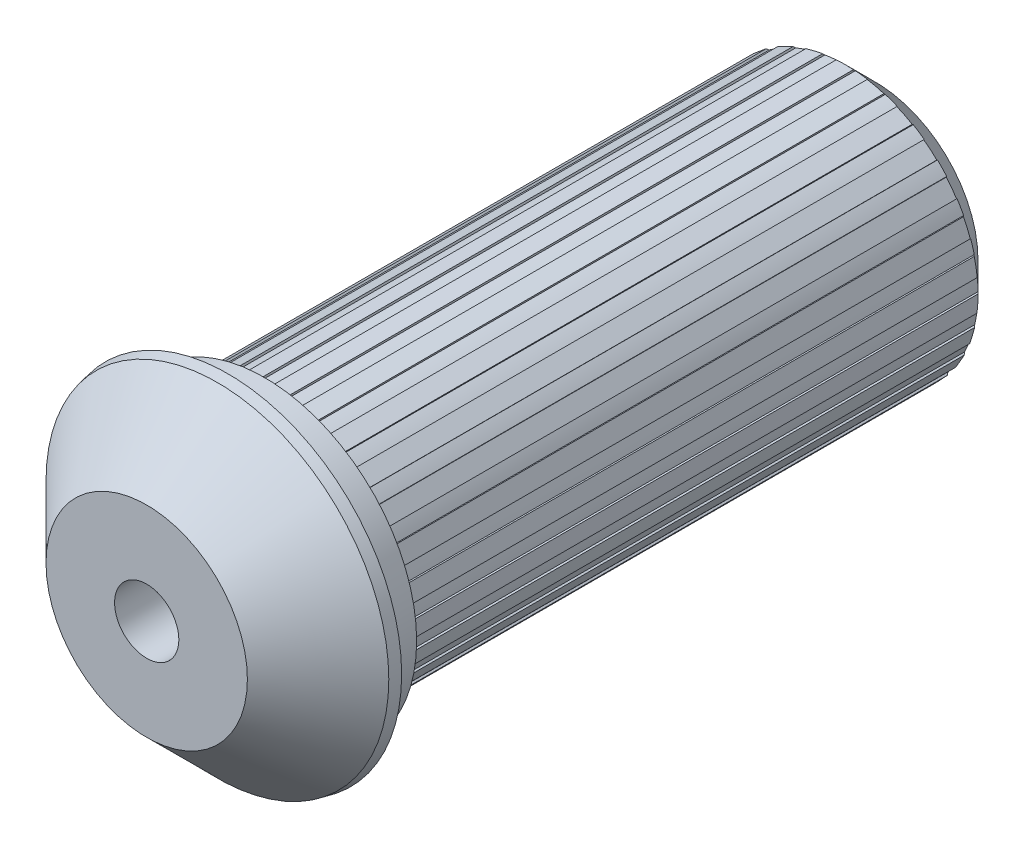
SolidWorks part; units mm, degrees
ref_plane "Front Plane" through (0, 0, 0) normal (0, 0, 1) x (1, 0, 0)
ref_plane "Top Plane" through (0, 0, 0) normal (0, 1, 0) x (1, 0, 0)
ref_plane "Right Plane" through (0, 0, 0) normal (1, 0, 0) x (0, 0, -1)
sketch "Sketch1" plane through (0, 0, 0) normal (0, 0, 1) x (1, 0, 0)
  line L0 (6.2, 2.4) -> (9.8, 2.4) construction
  line L1 (6.2, 2.4) -> (9.8, 2.4)
  arc A0 (6.2, 2.4) -> (9.8, 2.4) centre (8, 0) ccw construction
  arc A1 (6.2, 2.4) -> (9.8, 2.4) centre (8, 0) ccw
  circle A2 centre (8, 0) radius 6.075 construction
  circle A3 centre (8, 0) radius 6.075
extrude "Boss-Extrude1" add sketch "Sketch1" along normal up to surface (28.5 mm away)
sketch "Sketch2" plane through (0, 0, 28.5) normal (0, 0, 1) x (1, 0, 0)
  circle A0 centre (8, 0) radius 3
  circle A1 centre (8, 0) radius 1.5
  dimension "D1" = 3
extrude "Boss-Extrude2" add sketch "Sketch2" against normal up to surface (16.5 mm away)
sketch "Sketch3" plane through (0, 0, 28.5) normal (0, 0, 1) x (1, 0, 0)
  circle A0 centre (8, 0) radius 7.1 construction
  circle A1 centre (8, 0) radius 7.1
  circle A2 centre (8, 0) radius 1.5 construction
  circle A3 centre (8, 0) radius 1.5
extrude "Boss-Extrude3" add sketch "Sketch3" along normal offset from surface (5.5 mm away) 22 offset beyond the face yes
chamfer "Chamfer1" [suppressed] distance 1.2 angle 45
chamfer "Chamfer2" distance 2.4 angle 45 1 edges at (15.1, 0, 34)
sketch "Sketch4" plane through (0, 0, 0) normal (0, 0, -1) x (-1, 0, 0)
  circle A0 centre (-8, 0) radius 6.075 construction
  circle A1 centre (-8, 0) radius 6.075
  circle A2 centre (-8, 0) radius 6.125
  dimension "D1" = 12.25
extrude "Boss-Extrude4" add sketch "Sketch4" against normal up to surface (28.5 mm away) up to face at (15.1, 0, 28.5)
sketch "Sketch5" plane through (0, 0, 0) normal (0, 0, -1) x (-1, 0, 0)
  line L0 (-8, 0) -> (-8, 6.125) construction
  line L1 (-8, 0) -> (1.6155, 0) construction
  line L2 (-8.4, 6.05) -> (-7.6, 6.05)
  line L3 (-8.4, 6.05) -> (-8.4, 6.2)
  line L4 (-8.4, 6.2) -> (-7.6, 6.2)
  line L5 (-7.6, 6.05) -> (-7.6, 6.2)
  line L6 (-8.4, 6.05) -> (-7.6, 6.2) construction
  line L7 (-8.4, 6.2) -> (-7.6, 6.05) construction
  circle A0 centre (-8, 0) radius 6.125 construction
  dimension "D1" = 12.4
  dimension "D2" = 0.8
extrude "Boss-Extrude5" add sketch "Sketch5" against normal up to surface (28.5 mm away) up to face at (14.125, 0, 28.5)
pattern_circular "CirPattern1" count 27 over 360 about axis through (8, 0, 0) along (0, 0, 1) of "Boss-Extrude5"
sketch "Sketch6" plane through (0, 0, -27.3) normal (0, 1, 0) x (0, 0, 1)
  line L0 (61.3, 8) -> (24.9329, 8) construction
  line L1 (61.3, 3.3) -> (61.3, 12.7) construction
  line L2 (27.3, 12.8) -> (31.43, 16.93)
  line L3 (31.43, 16.93) -> (27.3, 16.93)
  line L4 (27.3, 16.93) -> (27.3, 12.8)
  line L5 (27.3, 11) -> (27.3, 5) construction
  line L6 (27.3, 11) -> (27.3, 5) construction
  dimension "D1" = 1.8
  dimension "D2" = 45
revolve "Cut-Revolve1" cut sketch "Sketch6" angle 360 about L0
sketch "Sketch7" plane through (0, 0, 0) normal (0, 1, 0) x (1, 0, 0)
  line L0 (8, -34) -> (8, -30.9231) construction
  line L1 (3.3, -34) -> (12.7, -34) construction
  line L2 (0.9, -31.6) -> (0.9, -30.2)
  line L3 (0.9, -28.5) -> (0.9, -31.6) construction
  line L4 (0.9, -30.2) -> (-0.1, -30.2)
  line L5 (-0.1, -30.2) -> (0, -30.7)
  line L6 (0, -30.7) -> (0.9, -31.6)
  line L7 (0.9, -31.6) -> (3.3, -34) construction
  dimension "D1" = 1.4
  dimension "D2" = 0.5
  dimension "D3" = 1
revolve "Revolve1" add sketch "Sketch7" angle 360 about L0
